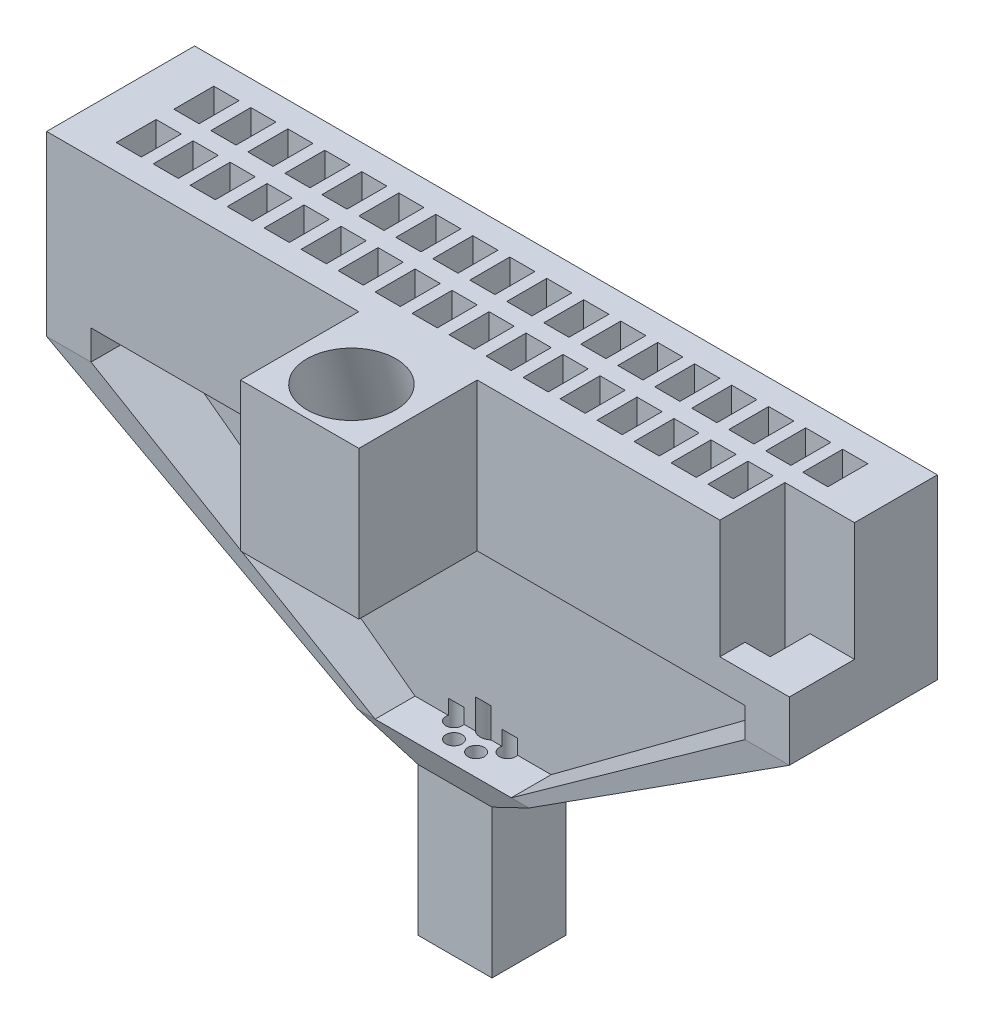
SolidWorks part; units mm, degrees
note: The reader was unsure of these and kept them because the rebuilt part matched: shared geometry of "Sketch13<3>".
ref_plane "Front Plane" through (0, 0, 0) normal (0, 0, 1) x (1, 0, 0)
ref_plane "Top Plane" through (0, 0, 0) normal (0, 1, 0) x (1, 0, 0)
ref_plane "Right Plane" through (0, 0, 0) normal (1, 0, 0) x (0, 0, -1)
sketch "main_block" plane through (0, 0, 0) normal (0, 1, 0) x (1, 0, 0)
  line L1 (-5.6188, 1.2192) -> (7.132, 1.2192)
  line L2 (-5.6188, 1.2192) -> (-5.6188, -1.3208)
  line L3 (-5.6188, -1.3208) -> (7.132, -1.3208)
  line L4 (7.132, 1.2192) -> (7.132, -1.3208)
  dimension "D1" = 12.7508
  dimension "D2" = 2.54
sketch "top_holes" plane through (0, 0, 0) normal (0, 1, 0) x (1, 0, 0)
  line L0 (7.132, 1.2192) -> (7.132, -1.3208) construction
  line L1 (6.37, 0.7874) -> (5.9382, 0.7874)
  line L2 (6.37, 0.7874) -> (6.37, 0.1016)
  line L3 (6.37, 0.1016) -> (5.9382, 0.1016)
  line L4 (5.9382, 0.7874) -> (5.9382, 0.1016)
  line L5 (-5.6188, 1.2192) -> (7.132, 1.2192) construction
  line L6 (5.3032, 0.7874) -> (5.3032, 0.1016)
  line L7 (5.735, 0.7874) -> (5.3032, 0.7874)
  line L8 (5.735, 0.7874) -> (5.735, 0.1016)
  line L9 (5.735, 0.1016) -> (5.3032, 0.1016)
  line L10 (4.6682, 0.7874) -> (4.6682, 0.1016)
  line L11 (5.1, 0.7874) -> (4.6682, 0.7874)
  line L12 (5.1, 0.7874) -> (5.1, 0.1016)
  line L13 (5.1, 0.1016) -> (4.6682, 0.1016)
  line L14 (4.0332, 0.7874) -> (4.0332, 0.1016)
  line L15 (4.465, 0.7874) -> (4.0332, 0.7874)
  line L16 (4.465, 0.7874) -> (4.465, 0.1016)
  line L17 (4.465, 0.1016) -> (4.0332, 0.1016)
  line L18 (3.3982, 0.7874) -> (3.3982, 0.1016)
  line L19 (3.83, 0.7874) -> (3.3982, 0.7874)
  line L20 (3.83, 0.7874) -> (3.83, 0.1016)
  line L21 (3.83, 0.1016) -> (3.3982, 0.1016)
  line L22 (2.7632, 0.7874) -> (2.7632, 0.1016)
  line L23 (3.195, 0.7874) -> (2.7632, 0.7874)
  line L24 (3.195, 0.7874) -> (3.195, 0.1016)
  line L25 (3.195, 0.1016) -> (2.7632, 0.1016)
  line L26 (2.1282, 0.7874) -> (2.1282, 0.1016)
  line L27 (2.56, 0.7874) -> (2.1282, 0.7874)
  line L28 (2.56, 0.7874) -> (2.56, 0.1016)
  line L29 (2.56, 0.1016) -> (2.1282, 0.1016)
  line L30 (1.4932, 0.7874) -> (1.4932, 0.1016)
  line L31 (1.925, 0.7874) -> (1.4932, 0.7874)
  line L32 (1.925, 0.7874) -> (1.925, 0.1016)
  line L33 (1.925, 0.1016) -> (1.4932, 0.1016)
  line L34 (0.8582, 0.7874) -> (0.8582, 0.1016)
  line L35 (1.29, 0.7874) -> (0.8582, 0.7874)
  line L36 (1.29, 0.7874) -> (1.29, 0.1016)
  line L37 (1.29, 0.1016) -> (0.8582, 0.1016)
  line L38 (0.2232, 0.7874) -> (0.2232, 0.1016)
  line L39 (0.655, 0.7874) -> (0.2232, 0.7874)
  line L40 (0.655, 0.7874) -> (0.655, 0.1016)
  line L41 (0.655, 0.1016) -> (0.2232, 0.1016)
  line L42 (-0.4117, 0.7874) -> (-0.4117, 0.1016)
  line L43 (0.0201, 0.7874) -> (-0.4117, 0.7874)
  line L44 (0.0201, 0.7874) -> (0.0201, 0.1016)
  line L45 (0.0201, 0.1016) -> (-0.4117, 0.1016)
  line L46 (-1.0467, 0.7874) -> (-1.0467, 0.1016)
  line L47 (-0.6149, 0.7874) -> (-1.0467, 0.7874)
  line L48 (-0.6149, 0.7874) -> (-0.6149, 0.1016)
  line L49 (-0.6149, 0.1016) -> (-1.0467, 0.1016)
  line L50 (-1.6817, 0.7874) -> (-1.6817, 0.1016)
  line L51 (-1.2499, 0.7874) -> (-1.6817, 0.7874)
  line L52 (-1.2499, 0.7874) -> (-1.2499, 0.1016)
  line L53 (-1.2499, 0.1016) -> (-1.6817, 0.1016)
  line L54 (-2.3167, 0.7874) -> (-2.3167, 0.1016)
  line L55 (-1.8849, 0.7874) -> (-2.3167, 0.7874)
  line L56 (-1.8849, 0.7874) -> (-1.8849, 0.1016)
  line L57 (-1.8849, 0.1016) -> (-2.3167, 0.1016)
  line L58 (-2.9517, 0.7874) -> (-2.9517, 0.1016)
  line L59 (-2.5199, 0.7874) -> (-2.9517, 0.7874)
  line L60 (-2.5199, 0.7874) -> (-2.5199, 0.1016)
  line L61 (-2.5199, 0.1016) -> (-2.9517, 0.1016)
  line L62 (-3.5867, 0.7874) -> (-3.5867, 0.1016)
  line L63 (-3.1549, 0.7874) -> (-3.5867, 0.7874)
  line L64 (-3.1549, 0.7874) -> (-3.1549, 0.1016)
  line L65 (-3.1549, 0.1016) -> (-3.5867, 0.1016)
  line L66 (-4.2217, 0.7874) -> (-4.2217, 0.1016)
  line L67 (-3.7899, 0.7874) -> (-4.2217, 0.7874)
  line L68 (-3.7899, 0.7874) -> (-3.7899, 0.1016)
  line L69 (-3.7899, 0.1016) -> (-4.2217, 0.1016)
  line L70 (-4.8567, 0.7874) -> (-4.8567, 0.1016)
  line L71 (-4.4249, 0.7874) -> (-4.8567, 0.7874)
  line L72 (-4.4249, 0.7874) -> (-4.4249, 0.1016)
  line L73 (-4.4249, 0.1016) -> (-4.8567, 0.1016)
  line L74 (5.3032, -0.2032) -> (5.3032, -0.889)
  line L75 (5.735, -0.2032) -> (5.3032, -0.2032)
  line L76 (5.735, -0.2032) -> (5.735, -0.889)
  line L77 (5.735, -0.889) -> (5.3032, -0.889)
  line L78 (4.6682, -0.2032) -> (4.6682, -0.889)
  line L79 (5.1, -0.2032) -> (4.6682, -0.2032)
  line L80 (5.1, -0.2032) -> (5.1, -0.889)
  line L81 (5.1, -0.889) -> (4.6682, -0.889)
  line L82 (4.0332, -0.2032) -> (4.0332, -0.889)
  line L83 (4.465, -0.2032) -> (4.0332, -0.2032)
  line L84 (4.465, -0.2032) -> (4.465, -0.889)
  line L85 (4.465, -0.889) -> (4.0332, -0.889)
  line L86 (3.3982, -0.2032) -> (3.3982, -0.889)
  line L87 (3.83, -0.2032) -> (3.3982, -0.2032)
  line L88 (3.83, -0.2032) -> (3.83, -0.889)
  line L89 (3.83, -0.889) -> (3.3982, -0.889)
  line L90 (2.7632, -0.2032) -> (2.7632, -0.889)
  line L91 (3.195, -0.2032) -> (2.7632, -0.2032)
  line L92 (3.195, -0.2032) -> (3.195, -0.889)
  line L93 (3.195, -0.889) -> (2.7632, -0.889)
  line L94 (2.1282, -0.2032) -> (2.1282, -0.889)
  line L95 (2.56, -0.2032) -> (2.1282, -0.2032)
  line L96 (2.56, -0.2032) -> (2.56, -0.889)
  line L97 (2.56, -0.889) -> (2.1282, -0.889)
  line L98 (1.4932, -0.2032) -> (1.4932, -0.889)
  line L99 (1.925, -0.2032) -> (1.4932, -0.2032)
  line L100 (1.925, -0.2032) -> (1.925, -0.889)
  line L101 (1.925, -0.889) -> (1.4932, -0.889)
  line L102 (0.8582, -0.2032) -> (0.8582, -0.889)
  line L103 (1.29, -0.2032) -> (0.8582, -0.2032)
  line L104 (1.29, -0.2032) -> (1.29, -0.889)
  line L105 (1.29, -0.889) -> (0.8582, -0.889)
  line L106 (0.2232, -0.2032) -> (0.2232, -0.889)
  line L107 (0.655, -0.2032) -> (0.2232, -0.2032)
  line L108 (0.655, -0.2032) -> (0.655, -0.889)
  line L109 (0.655, -0.889) -> (0.2232, -0.889)
  line L110 (-0.4117, -0.2032) -> (-0.4117, -0.889)
  line L111 (0.0201, -0.2032) -> (-0.4117, -0.2032)
  line L112 (0.0201, -0.2032) -> (0.0201, -0.889)
  line L113 (0.0201, -0.889) -> (-0.4117, -0.889)
  line L114 (-1.0467, -0.2032) -> (-1.0467, -0.889)
  line L115 (-0.6149, -0.2032) -> (-1.0467, -0.2032)
  line L116 (-0.6149, -0.2032) -> (-0.6149, -0.889)
  line L117 (-0.6149, -0.889) -> (-1.0467, -0.889)
  line L118 (-1.6817, -0.2032) -> (-1.6817, -0.889)
  line L119 (-1.2499, -0.2032) -> (-1.6817, -0.2032)
  line L120 (-1.2499, -0.2032) -> (-1.2499, -0.889)
  line L121 (-1.2499, -0.889) -> (-1.6817, -0.889)
  line L122 (-2.3167, -0.2032) -> (-2.3167, -0.889)
  line L123 (-1.8849, -0.2032) -> (-2.3167, -0.2032)
  line L124 (-1.8849, -0.2032) -> (-1.8849, -0.889)
  line L125 (-1.8849, -0.889) -> (-2.3167, -0.889)
  line L126 (-2.9517, -0.2032) -> (-2.9517, -0.889)
  line L127 (-2.5199, -0.2032) -> (-2.9517, -0.2032)
  line L128 (-2.5199, -0.2032) -> (-2.5199, -0.889)
  line L129 (-2.5199, -0.889) -> (-2.9517, -0.889)
  line L130 (-3.5867, -0.2032) -> (-3.5867, -0.889)
  line L131 (-3.1549, -0.2032) -> (-3.5867, -0.2032)
  line L132 (-3.1549, -0.2032) -> (-3.1549, -0.889)
  line L133 (-3.1549, -0.889) -> (-3.5867, -0.889)
  line L134 (-4.2217, -0.2032) -> (-4.2217, -0.889)
  line L135 (-3.7899, -0.2032) -> (-4.2217, -0.2032)
  line L136 (-3.7899, -0.2032) -> (-3.7899, -0.889)
  line L137 (-3.7899, -0.889) -> (-4.2217, -0.889)
  line L138 (-4.8567, -0.2032) -> (-4.8567, -0.889)
  line L139 (-4.4249, -0.2032) -> (-4.8567, -0.2032)
  line L140 (-4.4249, -0.2032) -> (-4.4249, -0.889)
  line L141 (-4.4249, -0.889) -> (-4.8567, -0.889)
  line L142 (5.9382, -0.2032) -> (5.9382, -0.889)
  line L143 (6.37, -0.2032) -> (5.9382, -0.2032)
  line L144 (6.37, -0.2032) -> (6.37, -0.889)
  line L145 (6.37, -0.889) -> (5.9382, -0.889)
  line L148 (-5.6188, 1.2192) -> (-5.6188, -1.3208) construction
  dimension "D1" = 0.4318
  dimension "D2" = 0.6858
  dimension "D3" = 0.762
  dimension "D4" = 0.4318
  dimension "D5" = 18
  dimension "D6" = 2
extrude "well_block" add sketch "main_block" against normal blind 2.54
extrude "omnetics_wells" cut sketch "top_holes" against normal blind 2.54
ref_plane "Plane1" through (0, -6.35, 0) normal (0, 1, 0) x (1, 0, 0)
sketch "Sketch4" plane through (0, -6.35, 0) normal (0, 1, 0) x (1, 0, 0)
  line L1 (1.9249, 0.889) -> (-0.4117, 0.889)
  line L2 (1.9249, 0.889) -> (1.9249, -0.889)
  line L3 (1.9249, -0.889) -> (-0.4117, -0.889)
  line L4 (-0.4117, 0.889) -> (-0.4117, -0.889)
  line L5 (1.9249, 0.889) -> (-0.4117, -0.889) construction
  line L6 (1.9249, -0.889) -> (-0.4117, 0.889) construction
  point P0 (0.7566, 0)
  dimension "D1" = 2.3367
  dimension "D2" = 1.778
sketch "Sketch5" plane through (0, -2.54, 0) normal (0, -1, 0) x (1, 0, 0)
  line L1 (-4.8567, 0.2032) -> (6.37, 0.2032)
  line L2 (-4.8567, 0.2032) -> (-4.8567, -0.1016)
  line L3 (-4.8567, -0.1016) -> (6.37, -0.1016)
  line L4 (6.37, 0.2032) -> (6.37, -0.1016)
sketch "Sketch6" plane through (0, -6.35, 0) normal (0, 1, 0) x (1, 0, 0)
  line L1 (-0.4117, 0.1016) -> (1.925, 0.1016)
  line L2 (-0.4117, 0.1016) -> (-0.4117, -0.2032)
  line L3 (-0.4117, -0.2032) -> (1.925, -0.2032)
  line L4 (1.925, 0.1016) -> (1.925, -0.2032)
sketch "Sketch7" plane through (0, -6.35, 0) normal (0, 1, 0) x (1, 0, 0)
  line L0 (-0.4117, -0.889) -> (-0.4117, 0.889)
  line L1 (-0.4117, -0.889) -> (-0.7165, -0.889)
  line L2 (-0.4117, 0.889) -> (-0.7165, 0.889)
  line L3 (-0.7165, -0.889) -> (-0.7165, 0.889)
  dimension "D1" = 0.3048
sketch "Sketch8" plane through (0, -2.54, 0) normal (0, -1, 0) x (1, 0, 0)
  line L0 (-4.8567, 1.3208) -> (-4.8567, -1.2192)
  line L1 (-4.8567, 1.3208) -> (-5.6187, 1.3208)
  line L2 (-4.8567, -1.2192) -> (-5.6187, -1.2192)
  line L3 (-5.6187, 1.3208) -> (-5.6187, -1.2192)
  line L4 (-5.6188, 1.3208) -> (7.132, 1.3208) construction
  line L5 (7.132, -1.2192) -> (-5.6188, -1.2192) construction
  dimension "D1" = 0.762
  dimension "D2" = 0
  dimension "D3" = 0
extrude "supportbeam1" add sketch "Sketch8" along normal blind 0.508
sketch "Sketch9" plane through (0, -6.35, 0) normal (0, 1, 0) x (1, 0, 0)
  line L0 (1.925, -0.889) -> (1.9249, 0.889)
  line L1 (1.925, -0.889) -> (2.2298, -0.889)
  line L2 (1.9249, 0.889) -> (2.2297, 0.889)
  line L3 (2.2298, -0.889) -> (2.2297, 0.889)
  dimension "D1" = 0.3048
sketch "Sketch10" plane through (0, -2.54, 0) normal (0, -1, 0) x (1, 0, 0)
  line L0 (6.37, -1.2192) -> (6.37, 1.3208)
  line L1 (6.37, -1.2192) -> (7.132, -1.2192)
  line L2 (6.37, 1.3208) -> (7.132, 1.3208)
  line L3 (7.132, -1.2192) -> (7.132, 1.3208)
  line L4 (-5.6188, 1.3208) -> (-5.6187, 1.3208) construction
  line L5 (7.132, -1.2192) -> (-4.8567, -1.2192) construction
  dimension "D1" = 0.762
  dimension "D2" = 0
  dimension "D3" = 0
extrude "supportbeam2" add sketch "Sketch10" along normal blind 0.508
loft "arm1" add profiles "Sketch9" section "Sketch9" section face at (6.751, -3.048, 0.0508) connector at (1.925, -6.35, 0.889) connector at (6.37, -3.048, 1.3208)
loft "arm2" add profiles "Sketch7" section "Sketch7" section face at (-5.2377, -3.048, 0.0508) connector at (-0.4117, -6.35, 0.889) connector at (-4.8567, -3.048, 1.3208)
extrude "wall_divider" add sketch "Sketch5" along normal blind 0.508
loft "wall_divider2" add profiles "Sketch6" section face at (0.7566, -3.048, 0.0508) section "Sketch6"
sketch "Sketch12" plane through (0, -6.35, 0) normal (0, 1, 0) x (1, 0, 0)
  line L1 (-0.7165, 0.889) -> (2.2299, 0.889)
  line L2 (-0.7165, 0.889) -> (-0.7165, -0.889)
  line L3 (-0.7165, -0.889) -> (2.2299, -0.889)
  line L4 (2.2299, 0.889) -> (2.2299, -0.889)
  line L6 (-0.4117, 0.889) -> (-0.7165, 0.889) construction
  line L7 (-0.7165, -0.889) -> (-0.4117, -0.889) construction
  dimension "D1" = 0
  dimension "D2" = 2.9464
  dimension "D3" = 0
ref_plane "Plane2" through (0, -6.858, 0) normal (0, 1, 0) x (1, 0, 0)
sketch "Sketch13" plane through (0, -6.858, 0) normal (0, 1, 0) x (1, 0, 0)
  line L0 (0.8582, -0.2032) -> (0.8582, -0.889) construction
  line L1 (1.3916, 0.5842) -> (0.1216, 0.5842)
  line L2 (1.3916, 0.5842) -> (1.3916, -0.6858)
  line L3 (1.3916, -0.6858) -> (0.1216, -0.6858)
  line L4 (0.1216, 0.5842) -> (0.1216, -0.6858)
  line L5 (1.3916, 0.5842) -> (0.1216, -0.6858) construction
  line L6 (1.3916, -0.6858) -> (0.1216, 0.5842) construction
  line L7 (0.655, -0.889) -> (0.655, -0.2032) construction
  line L8 (6.37, -0.2032) -> (1.925, -0.2032) construction
  line L9 (1.925, 0.1016) -> (6.37, 0.1016) construction
  point P0 (0.7566, 0)
  dimension "D1" = 1.27
  dimension "D2" = 1.27
  dimension "D3" = 0.4826
  dimension "D4" = 0.5334
  dimension "D5" = 0.5334
  dimension "D6" = 0.4826
loft "exit_base" add profiles "Sketch12", "Sketch13"
extrude "tetrode_funnel" add sketch "Sketch13<3>" against normal blind 2.54
sketch "Sketch13<3>" plane through (0, -6.858, 0) normal (0, 1, 0) x (1, 0, 0) same geometry as "Sketch13"
sketch "Sketch17" plane through (0, 0, 0) normal (0, 1, 0) x (1, 0, 0)
  line L1 (5.9382, -0.2032) -> (7.132, -0.2032)
  line L2 (5.9382, -0.2032) -> (5.9382, -1.3208)
  line L3 (5.9382, -1.3208) -> (7.132, -1.3208)
  line L4 (7.132, -0.2032) -> (7.132, -1.3208)
extrude "ground_wire_hole" cut sketch "Sketch17" against normal blind 2.032
sketch "Sketch18" plane through (0, -9.398, 0) normal (0, -1, 0) x (-1, 0, 0)
  line L0 (-0.1216, -0.6858) -> (-1.3916, -0.6858) construction
  line L1 (-1.3916, -0.6858) -> (-1.3916, 0.5842) construction
  line L2 (-1.3916, 0.5842) -> (-0.1216, 0.5842) construction
  circle A0 centre (-1.2138, -0.2413) radius 0.1397
  circle A1 centre (-1.2138, 0.1397) radius 0.1397
  circle A2 centre (-0.9444, 0.4091) radius 0.1397
  circle A3 centre (-0.5634, 0.4091) radius 0.1397
  circle A4 centre (-0.294, 0.1397) radius 0.1397
  circle A5 centre (-0.294, -0.2413) radius 0.1397
  circle A6 centre (-0.5634, -0.5107) radius 0.1397
  circle A7 centre (-0.9444, -0.5107) radius 0.1397
  point P18 (-0.7539, -0.0508)
  dimension "D1" = 8
  dimension "D2" = 0.4445
  dimension "D3" = 0.1778
  dimension "D4" = 0
  dimension "D5" = 0.381
  dimension "D6" = 0.4445
extrude "tetrodes" cut sketch "Sketch18" against normal blind 3.302
sketch "Sketch19" plane through (0, -9.398, 0) normal (0, -1, 0) x (1, 0, 0)
  line L0 (0.1216, -0.5842) -> (0.1216, 0.6858) construction
  line L1 (0.1216, 0.6858) -> (1.3916, 0.6858) construction
  circle A0 centre (0.7566, 0.0508) radius 0.2032
  point P2 (0.1216, 0.0508)
  dimension "D1" = 0.635
  dimension "D2" = 0.635
extrude "fiber_optic_hole" cut sketch "Sketch19" against normal blind 3.556
sketch "Sketch20" plane through (0, 0, 1.3208) normal (0, 0, 1) x (1, 0, 0)
  line L0 (-4.8567, -2.54) -> (6.37, -2.54) construction
  line L1 (-0.2594, -2.54) -> (1.7726, -2.54)
  line L2 (-0.2594, -2.54) -> (-0.2594, 0)
  line L3 (-0.2594, 0) -> (1.7726, 0)
  line L4 (1.7726, -2.54) -> (1.7726, 0)
  line L5 (-5.6188, -2.54) -> (-5.6188, 0) construction
  line L6 (7.132, -2.032) -> (7.132, 0) construction
  dimension "D1" = 2.54
  dimension "D2" = 2.032
  dimension "D3" = 5.3594
  dimension "D4" = 5.3594
extrude "fiber_optic_holder" add sketch "Sketch20" along normal blind 2.032
sketch "Sketch24" plane through (0, -2.54, 0) normal (0, -1, 0) x (1, 0, 0)
  line L0 (-0.2594, 3.3528) -> (1.7726, 3.3528) construction
  line L1 (-0.4117, 0.889) -> (1.925, 0.889) construction
  circle A0 centre (0.7606, 1.778) radius 0.762
  dimension "D1" = 0.889
sketch "Sketch25" plane through (0, 0, 0) normal (0, 1, 0) x (1, 0, 0)
  line L0 (1.7726, -3.3528) -> (-0.2594, -3.3528) construction
  circle A0 centre (0.7566, -2.4638) radius 0.762
  dimension "D1" = 0.889
loft "Cut-Loft1" cut profiles "Sketch24", "Sketch25" connector at (0.8724, -2.54, 2.5318) connector at (0.8398, 0, 3.2212)
